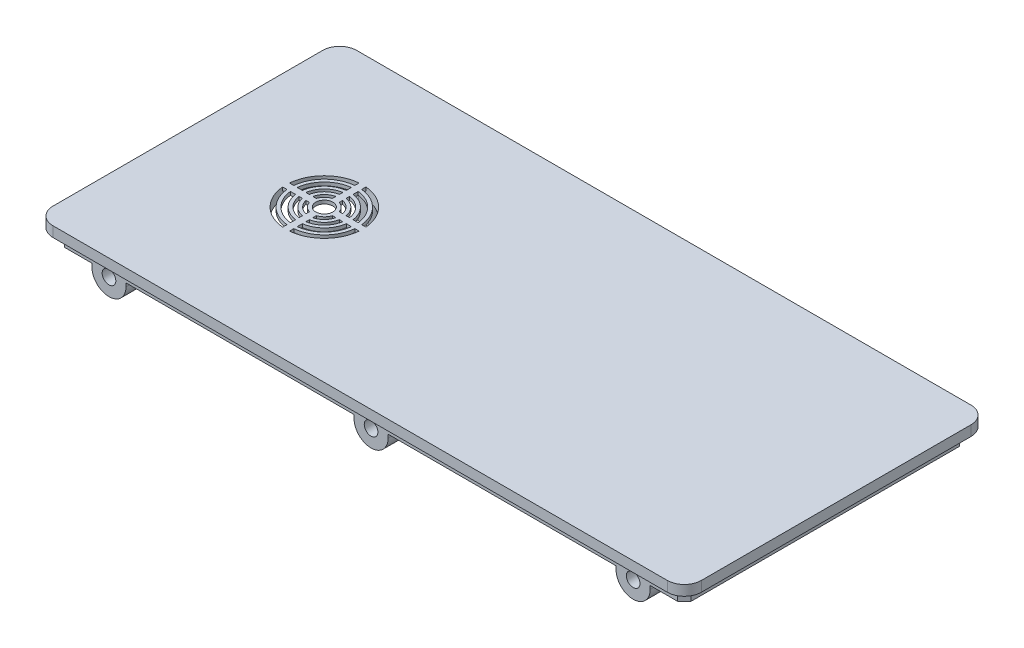
SolidWorks part; units mm, degrees
ref_plane "Front Plane" through (0, 0, 0) normal (0, 0, 1) x (1, 0, 0)
ref_plane "Top Plane" through (0, 0, 0) normal (0, 1, 0) x (1, 0, 0)
ref_plane "Right Plane" through (0, 0, 0) normal (1, 0, 0) x (0, 0, -1)
sketch "Sketch1" plane through (0, 0, 0) normal (0, 1, 0) x (1, 0, 0)
  line L1 (-95, 44.5) -> (95, 44.5)
  line L2 (-95, 44.5) -> (-95, -44.5)
  line L3 (-95, -44.5) -> (95, -44.5)
  line L4 (95, 44.5) -> (95, -44.5)
  line L5 (-95, 44.5) -> (95, -44.5) construction
  line L6 (-95, -44.5) -> (95, 44.5) construction
  point P0 (0, 0)
  dimension "D1" = 89
  dimension "D2" = 190
extrude "Boss-Extrude1" add sketch "Sketch1" along normal blind 3
sketch "Sketch2" plane through (0, 0, 0) normal (0, -1, 0) x (1, 0, 0)
  line L5 (-89.8, 39.3) -> (-89.8, -39.3)
  line L6 (-89.8, -39.3) -> (89.8, -39.3)
  line L7 (89.8, -39.3) -> (89.8, 39.3)
  line L8 (89.8, 39.3) -> (-89.8, 39.3)
  line L9 (-91.8, 41.3) -> (-91.8, -41.3)
  line L10 (-91.8, -41.3) -> (91.8, -41.3)
  line L11 (91.8, -41.3) -> (91.8, 41.3)
  line L12 (91.8, 41.3) -> (-91.8, 41.3)
  line L13 (-91.8, 41.3) -> (-91.8, -41.3)
  line L14 (-91.8, -41.3) -> (91.8, -41.3)
  line L15 (91.8, -41.3) -> (91.8, 41.3)
  line L16 (91.8, 41.3) -> (-91.8, 41.3)
  dimension "D1" = 3.2
  dimension "D2" = 2
extrude "Boss-Extrude2" add sketch "Sketch2" along normal blind 4
sketch "Sketch3" plane through (0, 0, -41.3) normal (0, 0, -1) x (-1, 0, 0)
  line L0 (91.8, 0) -> (-91.8, 0) construction
  line L1 (-81.8, 0) -> (-71.8, 0)
  line L2 (-81.8, 0) -> (-81.8, -10)
  line L3 (-81.8, -10) -> (-71.8, -10)
  line L4 (-71.8, 0) -> (-71.8, -10)
  line L5 (-91.8, -4) -> (-91.8, 0) construction
  line L6 (0, 0) -> (0, -43.8741) construction
  dimension "D1" = 10
  dimension "D2" = 10
  dimension "D3" = 10
extrude "Boss-Extrude3" add sketch "Sketch3" against normal blind 6
sketch "Sketch4" plane through (0, 0, -41.3) normal (0, 0, -1) x (-1, 0, 0)
  line L0 (-76.8, -10) -> (-76.8, 0) construction
  line L1 (-81.8, -10) -> (-71.8, -10) construction
  line L2 (91.8, 0) -> (-91.8, 0) construction
  circle A0 centre (-76.8, -5) radius 2
  dimension "D1" = 4
extrude "Cut-Extrude1" cut sketch "Sketch4" against normal blind 4
sketch "Sketch5" plane through (0, 0, -41.3) normal (0, 0, -1) x (-1, 0, 0)
  line L2 (-5, 0) -> (5, 0)
  line L3 (-5, 0) -> (-5, -10)
  line L4 (-5, -10) -> (5, -10)
  line L5 (5, 0) -> (5, -10)
  point P0 (0, 0)
  dimension "D1" = 10
  dimension "D2" = 10
extrude "Boss-Extrude4" add sketch "Sketch5" against normal blind 6
sketch "Sketch6" plane through (0, 0, -41.3) normal (0, 0, -1) x (-1, 0, 0)
  line L0 (0, 0) -> (0, -10) construction
  line L1 (-5, -10) -> (5, -10) construction
  circle A1 centre (0, -5) radius 2
  dimension "D1" = 4
extrude "Cut-Extrude2" cut sketch "Sketch6" against normal blind 4
mirror "Mirror1" about plane through (0, 0, 0) normal (1, 0, 0) of "Boss-Extrude3", "Cut-Extrude1" second plane through (0, 0, 0) second plane normal (0, 0, 1)
mirror "Mirror2" about plane through (0, 0, 0) normal (0, 0, 1) of "Cut-Extrude2", "Boss-Extrude4"
fillet "Fillet1" radius 5 24 edges at (76.8, -10, 41.3) (81.8, -10, 38.3) (71.8, -10, 38.3) (76.8, -10, 35.3) (-76.8, -10, -41.3) (-81.8, -10, -38.3) (-71.8, -10, -38.3) (-76.8, -10, -35.3) (-81.8, -10, 38.3) (-76.8, -10, 35.3) (-71.8, -10, 38.3) (-76.8, -10, 41.3) (0, -10, 41.3) (5, -10, 38.3) (-5, -10, 38.3) (0, -10, 35.3) (81.8, -10, -38.3) (76.8, -10, -35.3) (71.8, -10, -38.3) (76.8, -10, -41.3) (5, -10, -38.3) (0, -10, -35.3) (-5, -10, -38.3) (0, -10, -41.3)
fillet "Fillet3" radius 5 4 edges at (-95, 1.5, 44.5) (95, 1.5, 44.5) (95, 1.5, -44.5) (-95, 1.5, -44.5)
chamfer "Chamfer1" distance 2 angle 45 4 edges at (91.8, -2, 41.3) (-91.8, -2, -41.3) (-91.8, -2, 41.3) (91.8, -2, -41.3)
sketch "Sketch7" plane through (0, 0, 0) normal (0, -1, 0) x (1, 0, 0)
  line L0 (-95, 0) -> (95, 0) construction
  line L2 (-95, -39.5) -> (-95, 39.5) construction
  line L3 (95, 39.5) -> (95, -39.5) construction
  circle A0 centre (-55, 0) radius 11.25
  point P9 (0, 0)
  dimension "D1" = 22.5
  dimension "D2" = 40
extrude "Cut-Extrude3" cut sketch "Sketch7" against normal up to next
sketch "Sketch8" plane through (0, 3, 0) normal (0, 1, 0) x (1, 0, 0)
  line L0 (-54, -1) -> (-54, -15)
  line L1 (-70, 1) -> (-56, 1)
  line L2 (-70, 1) -> (-70, -1)
  line L3 (-70, -1) -> (-56, -1)
  line L4 (-40, 1) -> (-40, -1)
  line L5 (-70, 1) -> (-40, -1) construction
  line L6 (-70, -1) -> (-40, 1) construction
  line L7 (-56, 15) -> (-54, 15)
  line L8 (-56, 15) -> (-56, 1)
  line L9 (-56, -15) -> (-54, -15)
  line L10 (-54, 15) -> (-54, 1)
  line L11 (-56, 15) -> (-54, -15) construction
  line L12 (-56, -15) -> (-54, 15) construction
  line L13 (-54, -1) -> (-40, -1)
  line L14 (-54, 1) -> (-40, 1)
  line L15 (-56, -1) -> (-56, -15)
  circle A0 centre (-55, 0) radius 10 construction
  dimension "D1" = 20
  dimension "D2" = 30
  dimension "D3" = 2
  dimension "D4" = 2
  dimension "D5" = 30
extrude "Boss-Extrude5" add sketch "Sketch8" against normal blind 1
sketch "Sketch9" plane through (0, 3, 0) normal (0, 1, 0) x (1, 0, 0)
  circle A0 centre (-55, 0) radius 10
  circle A2 centre (-55, 0) radius 9
  dimension "D1" = 20
  dimension "D2" = 1
extrude "Boss-Extrude6" add sketch "Sketch9" against normal blind 1
sketch "Sketch10" plane through (0, 3, 0) normal (0, 1, 0) x (1, 0, 0)
  circle A0 centre (-55, 0) radius 7.5
  circle A1 centre (-55, 0) radius 6.5
  dimension "D1" = 15
  dimension "D2" = 1
extrude "Boss-Extrude7" add sketch "Sketch10" against normal blind 1
sketch "Sketch11" plane through (0, 3, 0) normal (0, 1, 0) x (1, 0, 0)
  circle A0 centre (-55, 0) radius 5.5
  circle A1 centre (-55, 0) radius 4.5
  dimension "D1" = 11
  dimension "D2" = 1
extrude "Boss-Extrude8" add sketch "Sketch11" against normal blind 1
sketch "Sketch12" plane through (0, 3, 0) normal (0, 1, 0) x (1, 0, 0)
  circle A0 centre (-55, 0) radius 3.5
  circle A1 centre (-55, 0) radius 2.5
  dimension "D1" = 7
  dimension "D2" = 1
extrude "Boss-Extrude9" add sketch "Sketch12" against normal blind 1
sketch "Sketch13" plane through (0, 3, 0) normal (0, 1, 0) x (1, 0, 0)
  circle A0 centre (-55, 0) radius 2.5
  dimension "D1" = 5
extrude "Cut-Extrude4" cut sketch "Sketch13" against normal up to next
sketch "Sketch16" plane through (0, 0, 0) normal (0, -1, 0) x (1, 0, 0)
  line L4 (-58.5, -11.5) -> (-51.5, -11.5)
  line L6 (-58.5, -11.5) -> (-58.5, -18.5)
  line L8 (-58.5, -18.5) -> (-51.5, -18.5)
  line L9 (-51.5, -11.5) -> (-51.5, -18.5)
  line L10 (-58.5, -11.5) -> (-51.5, -18.5) construction
  line L11 (-58.5, -18.5) -> (-51.5, -11.5) construction
  line L13 (90, -44.5) -> (-90, -44.5) construction
  line L14 (-95, -39.5) -> (-95, 39.5) construction
  line L15 (-90, 44.5) -> (90, 44.5) construction
  line L16 (-58.5, 18.5) -> (-51.5, 18.5)
  line L17 (-58.5, 18.5) -> (-58.5, 11.5)
  line L18 (-58.5, 11.5) -> (-51.5, 11.5)
  line L19 (-51.5, 18.5) -> (-51.5, 11.5)
  line L20 (-58.5, 18.5) -> (-51.5, 11.5) construction
  line L21 (-58.5, 11.5) -> (-51.5, 18.5) construction
  point P0 (-55, -15)
  point P12 (-55, 15)
  dimension "D1" = 29.5
  dimension "D2" = 40
  dimension "D3" = 40
  dimension "D4" = 29.5
  dimension "D5" = 7
  dimension "D6" = 7
  dimension "D7" = 7
  dimension "D8" = 7
extrude "Boss-Extrude11" add sketch "Sketch16" along normal blind 7
sketch "Sketch17" plane through (0, -7, 0) normal (0, -1, 0) x (1, 0, 0)
  line L0 (-55, -18.5) -> (-55, -11.5) construction
  line L1 (-58.5, -18.5) -> (-51.5, -18.5) construction
  line L2 (-51.5, -11.5) -> (-58.5, -11.5) construction
  line L3 (-55, 18.5) -> (-55, 11.5) construction
  line L4 (-51.5, 18.5) -> (-58.5, 18.5) construction
  line L5 (-58.5, 11.5) -> (-51.5, 11.5) construction
  circle A0 centre (-55, 15) radius 2
  circle A1 centre (-55, -15) radius 2
  dimension "D1" = 4
  dimension "D2" = 4
extrude "Cut-Extrude5" cut sketch "Sketch17" against normal blind 4 contours A1
mirror "Mirror3" about plane through (0, 0, 0) normal (0, 0, 1) of "Cut-Extrude5"
ref_plane "Plane1" through (-55, 0, 0) normal (1, 0, 0) x (0, 0, -1)
sketch "Sketch19" plane through (-55, 0, 0) normal (1, 0, 0) x (0, 0, -1)
  line L0 (18.5, -7) -> (22.5, 0)
  line L1 (39.5, 0) -> (-39.5, 0) construction
  line L2 (18.5, -7) -> (18.5, 0)
  line L3 (18.5, 0) -> (22.5, 0)
  dimension "D1" = 4
extrude "Boss-Extrude12" add sketch "Sketch19" along normal mid plane 3
fillet "Fillet4" radius 2 8 edges at (-58.5, -3.5, -11.5) (-51.5, -3.5, -11.5) (-51.5, -3.5, -18.5) (-58.5, -3.5, -18.5) (-58.5, -3.5, 18.5) (-51.5, -3.5, 18.5) (-51.5, -3.5, 11.5) (-58.5, -3.5, 11.5)
mirror "Mirror4" about plane through (0, 0, 0) normal (0, 0, 1) of "Boss-Extrude12"
ref_point "Point2"
ref_point "Point4"
ref_plane "Plane2" through (0, 0, 0) normal (-1, 0, 0) x (0, 0, 1)
sketch "Sketch20" plane through (0, 0, 0) normal (-1, 0, 0) x (0, 0, 1)
  line L0 (-35.3, -10) -> (-30.3, 0)
  line L1 (39.3, 0) -> (-39.3, 0) construction
  line L2 (-35.3, -10) -> (-35.3, 0)
  line L3 (-35.3, 0) -> (-30.3, 0)
  dimension "D1" = 5
extrude "Boss-Extrude13" add sketch "Sketch20" along normal mid plane 3
mirror "Mirror5" about plane through (0, 0, 0) normal (0, 0, 1) of "Boss-Extrude13"
pattern_linear "LPattern1" count 2 spacing 76.8 along (-1, 0, 0) count 2 spacing 76.8 along (1, 0, 0) of "Mirror5", "Boss-Extrude13"
